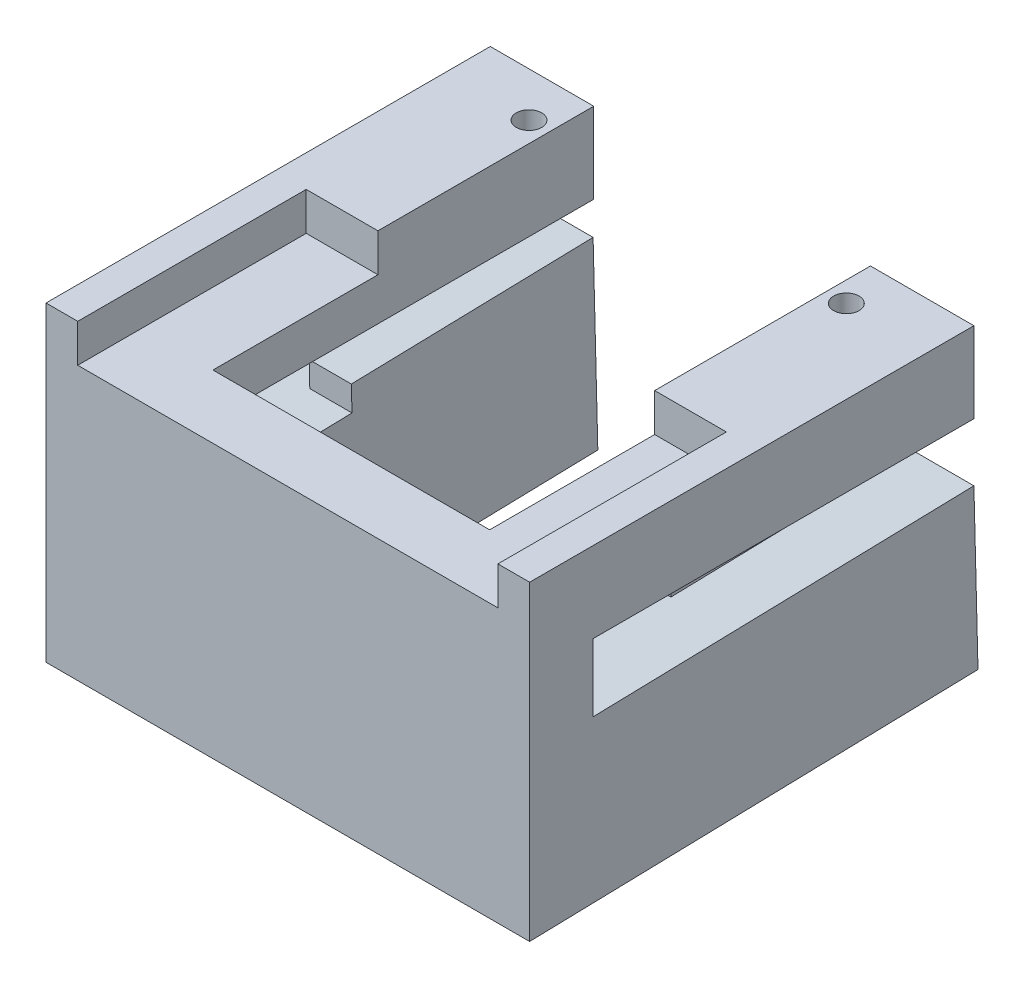
SolidWorks part; units mm, degrees
ref_plane "Front Plane" through (0, 0, 0) normal (0, 0, 1) x (1, 0, 0)
ref_plane "Top Plane" through (0, 0, 0) normal (0, 1, 0) x (1, 0, 0)
ref_plane "Right Plane" through (0, 0, 0) normal (1, 0, 0) x (0, 0, -1)
sketch "Sketch1" plane through (0, 0, 0) normal (1, 0, 0) x (0, 0, -1)
  line L0 (0, 7.406) -> (0, -7.406)
  line L1 (0, -7.406) -> (35.0762, -6.515)
  line L2 (35.0762, -6.515) -> (35, -3.516)
  line L3 (35, -3.516) -> (5, -4.278)
  line L4 (5, -4.278) -> (5, 1.056)
  line L5 (5, 1.056) -> (35, 1.056)
  line L6 (35, 1.056) -> (35, 7.406)
  line L7 (35, 7.406) -> (0, 7.406)
  line L8 (0, -7.406) -> (0, -17.1091)
  line L9 (0, -17.1091) -> (35.3225, -16.2119)
  line L10 (35.3225, -16.2119) -> (35.0762, -6.515)
  point P4 (0, 0)
  dimension "D1" = 5.334
  dimension "D2" = 4.572
  dimension "D3" = 3
  dimension "D4" = 5
  dimension "D5" = 6.35
  dimension "D6" = 35
  dimension "D7" = 12.7
extrude "Boss-Extrude1" add sketch "Sketch1" along normal mid plane 38.1 contours L6 L7 L0 L1 L2 L3 L4 L5 | L9 L10 L1 L8 region at (0, 7.0252, -17.5) region at (0, -11.8162, -17.5997)
sketch "Sketch2" plane through (0, 7.406, 0) normal (0, 1, 0) x (1, 0, 0)
  line L0 (-12.5, 31.5) -> (12.5, 31.5) construction
  line L1 (0, 31.5) -> (0, 35) construction
  line L2 (19.05, 35) -> (-19.05, 35) construction
  line L3 (0, 35) -> (0, 31.5) construction
  line L4 (-10.9, 37.9788) -> (10.9, 37.9788)
  line L5 (-10.9, 37.9788) -> (-10.9, 5)
  line L6 (-10.9, 5) -> (10.9, 5)
  line L7 (10.9, 37.9788) -> (10.9, 5)
  circle A0 centre (-12.5, 31.5) radius 1
  circle A1 centre (12.5, 31.5) radius 1
  point P12 (0, 37.9788)
  dimension "D1" = 2
  dimension "D2" = 25
  dimension "D3" = 3.5
  dimension "D4" = 21.8
extrude "Cut-Extrude1" cut sketch "Sketch2" against normal through all
sketch "Sketch3" plane through (0, 7.406, 0) normal (0, 1, 0) x (1, 0, 0)
  line L1 (-16.55, 18) -> (16.55, 18)
  line L2 (-16.55, 18) -> (-16.55, 0)
  line L3 (-16.55, 0) -> (16.55, 0)
  line L4 (16.55, 18) -> (16.55, 0)
  line L5 (0, 18) -> (0, 0) construction
  line L6 (19.05, 0) -> (-19.05, 0) construction
  line L9 (-19.05, 35) -> (-19.05, 0) construction
  dimension "D1" = 2.5
  dimension "D2" = 18
extrude "Cut-Extrude2" cut sketch "Sketch3" against normal blind 3
sketch "Sketch4" plane through (0, -4.4022, -0.1118) normal (0, 0.9997, 0.0254) x (1, 0, 0)
  line L1 (14.224, 34.8994) -> (10.9, 34.8994)
  line L2 (14.224, 34.8994) -> (14.224, 15.8494)
  line L3 (14.224, 15.8494) -> (10.9, 15.8494)
  line L4 (10.9, 34.8994) -> (10.9, 15.8494)
  line L5 (-14.224, 15.8494) -> (-10.9, 15.8494)
  line L6 (-14.224, 15.8494) -> (-14.224, 34.8994)
  line L7 (-14.224, 34.8994) -> (-10.9, 34.8994)
  line L8 (-10.9, 15.8494) -> (-10.9, 34.8994)
  line L9 (-10.9, 34.8994) -> (-19.05, 34.8994) construction
  line L10 (19.05, 34.8994) -> (10.9, 34.8994) construction
  dimension "D1" = 28.448
  dimension "D2" = 19.05
extrude "Boss-Extrude2" add sketch "Sketch4" along normal blind 2 and the other way up to surface (12.7 mm away) other way up to face at (-12.5, -16.2836, -32.5)
